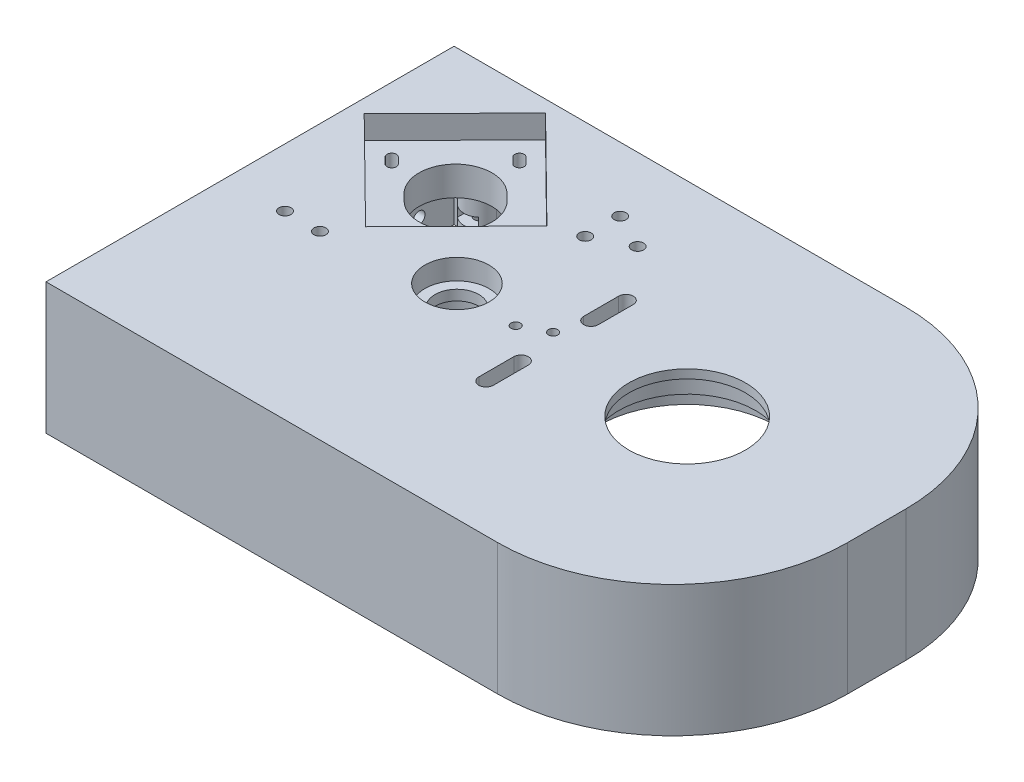
SolidWorks part; units mm, degrees
ref_plane "Front Plane" through (0, 0, 0) normal (0, 0, 1) x (1, 0, 0)
ref_plane "Top Plane" through (0, 0, 0) normal (0, 1, 0) x (1, 0, 0)
ref_plane "Right Plane" through (0, 0, 0) normal (1, 0, 0) x (0, 0, -1)
sketch "Sketch1" plane through (0, 0, 0) normal (0, 1, 0) x (1, 0, 0)
  line L1 (-107.5, -70) -> (107.5, -70)
  line L2 (-107.5, -70) -> (-107.5, 70)
  line L3 (-107.5, 70) -> (107.5, 70)
  line L4 (107.5, -70) -> (107.5, 70)
  line L5 (-107.5, -70) -> (107.5, 70) construction
  line L6 (-107.5, 70) -> (107.5, -70) construction
  point P0 (0, 0)
  dimension "D1" = 215
  dimension "D2" = 140
extrude "Boss-Extrude1" add sketch "Sketch1" along normal blind 10
fillet "Fillet1" radius 60 2 edges at (107.5, 5, -70) (107.5, 5, 70)
sketch "Sketch2" plane through (0, 10, 0) normal (0, 1, 0) x (1, 0, 0)
  line L0 (107.5, -10) -> (107.5, 10) construction
  line L1 (30.0949, 32.7279) -> (-38.981, 6.5456) construction
  line L2 (-38.981, -6.5456) -> (30.0949, -32.7279) construction
  circle A0 centre (42.5, 0) radius 20
  arc A1 (-38.981, 6.5456) -> (-38.981, -6.5456) centre (-36.5, 0) ccw construction
  circle A2 centre (-36.5, 0) radius 7.5
  arc A3 (30.0949, -32.7279) -> (30.0949, 32.7279) centre (42.5, 0) ccw construction
  dimension "D1" = 40
  dimension "D3" = 14
  dimension "D5" = 70
  dimension "D6" = 15
  dimension "D2" = 65
  dimension "D4" = 79
extrude "Cut-Extrude1" cut sketch "Sketch2" against normal through all
sketch "Sketch3" plane through (0, 10, 0) normal (0, 1, 0) x (1, 0, 0)
  line L0 (-36.5, 0) -> (-107.5, 70) construction
  line L1 (-67.0785, 38.2761) -> (-27.7732, 23.9602) construction
  line L2 (-75.2059, 30.0325) -> (-60.334, -9.0658) construction
  line L3 (-62.6172, 43.3029) -> (-60.4808, 41.1967)
  line L4 (-80.169, 25.5003) -> (-78.0327, 23.3941)
  arc A0 (-78.0327, 23.3941) -> (-60.4808, 41.1967) centre (-69.2568, 32.2954) ccw
  arc A1 (-67.0785, 38.2761) -> (-75.2059, 30.0325) centre (-69.2568, 32.2954) ccw construction
  arc A2 (-60.334, -9.0658) -> (-27.7732, 23.9602) centre (-36.5, 0) ccw construction
  arc A3 (-62.6172, 43.3029) -> (-80.169, 25.5003) centre (-71.3931, 34.4016) ccw
  dimension "D1" = 25
  dimension "D2" = 51
  dimension "D3" = 12.73
  dimension "D6" = 25
  dimension "D4" = 46
  dimension "D5" = 3
extrude "Cut-Extrude2" cut sketch "Sketch3" against normal through all
sketch "Sketch4" plane through (0, 10, 0) normal (0, 1, 0) x (1, 0, 0)
  line L0 (-47.3365, 32.2954) -> (-49.4578, 34.4167) construction
  line L1 (-91.1771, 32.2954) -> (-69.2568, 10.3751) construction
  line L2 (-91.1771, 32.2954) -> (-69.2568, 54.2157) construction
  line L3 (-69.2568, 54.2157) -> (-47.3365, 32.2954) construction
  line L4 (-69.2568, 10.3751) -> (-47.3365, 32.2954) construction
  line L5 (-91.1771, 32.2954) -> (-47.3365, 32.2954) construction
  line L6 (-69.2568, 54.2157) -> (-69.2568, 10.3751) construction
  line L7 (-48.4678, 31.164) -> (-50.5892, 33.2854)
  line L8 (-46.2051, 33.4268) -> (-48.3264, 35.5481)
  line L9 (-69.2568, 54.2157) -> (-71.3781, 56.337) construction
  line L10 (-70.3881, 53.0844) -> (-72.5095, 55.2057)
  line L11 (-68.1254, 55.3471) -> (-70.2467, 57.4684)
  line L12 (-69.2568, 10.3751) -> (-71.3781, 12.4964) construction
  line L13 (-70.3881, 9.2437) -> (-72.5095, 11.3651)
  line L14 (-68.1254, 11.5065) -> (-70.2467, 13.6278)
  line L15 (-91.1771, 32.2954) -> (-93.2984, 34.4167) construction
  line L16 (-92.3085, 31.164) -> (-94.4298, 33.2854)
  line L17 (-90.0457, 33.4268) -> (-92.167, 35.5481)
  line L18 (47.5, 70) -> (-107.5, 70) construction
  arc A0 (-48.4678, 31.164) -> (-46.2051, 33.4268) centre (-47.3365, 32.2954) ccw
  arc A1 (-48.3264, 35.5481) -> (-50.5892, 33.2854) centre (-49.4578, 34.4167) ccw
  arc A2 (-70.3881, 53.0844) -> (-68.1254, 55.3471) centre (-69.2568, 54.2157) ccw
  arc A3 (-70.2467, 57.4684) -> (-72.5095, 55.2057) centre (-71.3781, 56.337) ccw
  arc A4 (-70.3881, 9.2437) -> (-68.1254, 11.5065) centre (-69.2568, 10.3751) ccw
  arc A5 (-70.2467, 13.6278) -> (-72.5095, 11.3651) centre (-71.3781, 12.4964) ccw
  arc A6 (-92.3085, 31.164) -> (-90.0457, 33.4268) centre (-91.1771, 32.2954) ccw
  arc A7 (-92.167, 35.5481) -> (-94.4298, 33.2854) centre (-93.2984, 34.4167) ccw
  point P0 (-69.2568, 32.2954)
  point P6 (-48.3971, 33.3561)
  point P12 (-70.3174, 55.2764)
  point P18 (-70.3174, 11.4358)
  point P24 (-92.2377, 33.3561)
  dimension "D3" = 1.6
  dimension "D5" = 1.6
  dimension "D7" = 1.6
  dimension "D9" = 1.6
  dimension "D1" = 31
  dimension "D2" = 31
  dimension "D4" = 3
  dimension "D6" = 3
  dimension "D8" = 3
  dimension "D10" = 3
  dimension "D11" = 45
extrude "Cut-Extrude3" cut sketch "Sketch4" against normal through all
sketch "Sketch5" plane through (0, 10, 0) normal (0, 1, 0) x (1, 0, 0)
  circle A0 centre (-36.5, 0) radius 11
  dimension "D1" = 22
extrude "Cut-Extrude4" cut sketch "Sketch5" against normal blind 7
sketch "Sketch6" plane through (0, 0, 0) normal (0, -1, 0) x (1, 0, 0)
  circle A0 centre (-36.5, 0) radius 11
  circle A1 centre (-36.5, 0) radius 14
  dimension "D1" = 22
  dimension "D2" = 3
extrude "Boss-Extrude2" add sketch "Sketch6" along normal blind 8.5
sketch "Sketch7" plane through (0, 0, 0) normal (0, -1, 0) x (1, 0, 0)
  circle A0 centre (42.5, 0) radius 23.5
  dimension "D1" = 47
extrude "Cut-Extrude5" cut sketch "Sketch7" against normal blind 7
sketch "Sketch8" plane through (0, 0, 0) normal (0, -1, 0) x (1, 0, 0)
  circle A0 centre (42.5, 0) radius 30.5
  circle A1 centre (42.5, 0) radius 38.5
  dimension "D1" = 61
  dimension "D2" = 8
extrude "Boss-Extrude3" add sketch "Sketch8" along normal blind 8
sketch "Sketch9" plane through (0, 0, 0) normal (0, -1, 0) x (1, 0, 0)
  line L0 (47.5, 62) -> (-99.5, 62)
  line L1 (-99.5, 62) -> (-99.5, -62)
  line L2 (-99.5, -62) -> (47.5, -62)
  line L3 (99.5, -10) -> (99.5, 10)
  line L4 (-107.5, -70) -> (47.5, -70)
  line L5 (107.5, -10) -> (107.5, 10)
  line L6 (47.5, 70) -> (-107.5, 70)
  line L7 (-107.5, 70) -> (-107.5, -70)
  line L8 (-107.5, -70) -> (47.5, -70)
  line L9 (107.5, -10) -> (107.5, 10)
  line L10 (47.5, 70) -> (-107.5, 70)
  line L11 (-107.5, 70) -> (-107.5, -70)
  arc A0 (47.5, -62) -> (99.5, -10) centre (47.5, -10) ccw
  arc A1 (99.5, 10) -> (47.5, 62) centre (47.5, 10) ccw
  arc A2 (47.5, -70) -> (107.5, -10) centre (47.5, -10) ccw
  arc A3 (107.5, 10) -> (47.5, 70) centre (47.5, 10) ccw
  arc A4 (47.5, -70) -> (107.5, -10) centre (47.5, -10) ccw
  arc A5 (107.5, 10) -> (47.5, 70) centre (47.5, 10) ccw
  dimension "D1" = 0
  dimension "D2" = 8
extrude "Boss-Extrude4" add sketch "Sketch9" along normal blind 35
sketch "Sketch10" plane through (0, 0, 0) normal (0, -1, 0) x (1, 0, 0)
  line L0 (-36.5, -14) -> (-36.5, -62)
  line L1 (-99.5, -62) -> (47.5, -62) construction
  line L2 (-50.5, 0) -> (-99.5, 0)
  line L3 (-99.5, 62) -> (-99.5, -62) construction
  line L4 (-99.5, 0) -> (-99.5, -62)
  line L5 (-99.5, -62) -> (-36.5, -62)
  line L6 (-80.169, -25.5003) -> (-78.0327, -23.3941) construction
  line L7 (-80.169, -25.5003) -> (-78.0327, -23.3941)
  line L8 (-60.4808, -41.1967) -> (-62.6172, -43.3029) construction
  line L9 (-94.4298, -33.2854) -> (-92.3085, -31.164) construction
  line L10 (-90.0457, -33.4268) -> (-92.167, -35.5481) construction
  line L11 (-68.1254, -55.3471) -> (-70.2467, -57.4684) construction
  line L12 (-72.5095, -55.2057) -> (-70.3881, -53.0844) construction
  line L13 (-46.2051, -33.4268) -> (-48.3264, -35.5481) construction
  line L14 (-50.5892, -33.2854) -> (-48.4678, -31.164) construction
  line L15 (-68.1254, -11.5065) -> (-70.2467, -13.6278) construction
  line L16 (-72.5095, -11.3651) -> (-70.3881, -9.2437) construction
  line L17 (-60.4808, -41.1967) -> (-62.6172, -43.3029)
  line L18 (-94.4298, -33.2854) -> (-92.3085, -31.164)
  line L19 (-90.0457, -33.4268) -> (-92.167, -35.5481)
  line L20 (-68.1254, -55.3471) -> (-70.2467, -57.4684)
  line L21 (-72.5095, -55.2057) -> (-70.3881, -53.0844)
  line L22 (-46.2051, -33.4268) -> (-48.3264, -35.5481)
  line L23 (-50.5892, -33.2854) -> (-48.4678, -31.164)
  line L24 (-68.1254, -11.5065) -> (-70.2467, -13.6278)
  line L25 (-72.5095, -11.3651) -> (-70.3881, -9.2437)
  circle A0 centre (-36.5, 0) radius 14 construction
  circle A1 centre (-36.5, 0) radius 14 construction
  arc A2 (-50.5, 0) -> (-36.5, -14) centre (-36.5, 0) ccw
  arc A3 (-60.4808, -41.1967) -> (-78.0327, -23.3941) centre (-69.2568, -32.2954) ccw construction
  arc A4 (-80.169, -25.5003) -> (-62.6172, -43.3029) centre (-71.3931, -34.4016) ccw construction
  arc A5 (-90.0457, -33.4268) -> (-92.3085, -31.164) centre (-91.1771, -32.2954) ccw construction
  arc A6 (-94.4298, -33.2854) -> (-92.167, -35.5481) centre (-93.2984, -34.4167) ccw construction
  arc A7 (-72.5095, -55.2057) -> (-70.2467, -57.4684) centre (-71.3781, -56.337) ccw construction
  arc A8 (-68.1254, -55.3471) -> (-70.3881, -53.0844) centre (-69.2568, -54.2157) ccw construction
  arc A9 (-50.5892, -33.2854) -> (-48.3264, -35.5481) centre (-49.4578, -34.4167) ccw construction
  arc A10 (-46.2051, -33.4268) -> (-48.4678, -31.164) centre (-47.3365, -32.2954) ccw construction
  arc A11 (-72.5095, -11.3651) -> (-70.2467, -13.6278) centre (-71.3781, -12.4964) ccw construction
  arc A12 (-68.1254, -11.5065) -> (-70.3881, -9.2437) centre (-69.2568, -10.3751) ccw construction
  arc A13 (-60.4808, -41.1967) -> (-78.0327, -23.3941) centre (-69.2568, -32.2954) ccw
  arc A14 (-80.169, -25.5003) -> (-62.6172, -43.3029) centre (-71.3931, -34.4016) ccw
  arc A15 (-90.0457, -33.4268) -> (-92.3085, -31.164) centre (-91.1771, -32.2954) ccw
  arc A16 (-94.4298, -33.2854) -> (-92.167, -35.5481) centre (-93.2984, -34.4167) ccw
  arc A17 (-72.5095, -55.2057) -> (-70.2467, -57.4684) centre (-71.3781, -56.337) ccw
  arc A18 (-68.1254, -55.3471) -> (-70.3881, -53.0844) centre (-69.2568, -54.2157) ccw
  arc A19 (-50.5892, -33.2854) -> (-48.3264, -35.5481) centre (-49.4578, -34.4167) ccw
  arc A20 (-46.2051, -33.4268) -> (-48.4678, -31.164) centre (-47.3365, -32.2954) ccw
  arc A21 (-72.5095, -11.3651) -> (-70.2467, -13.6278) centre (-71.3781, -12.4964) ccw
  arc A22 (-68.1254, -11.5065) -> (-70.3881, -9.2437) centre (-69.2568, -10.3751) ccw
extrude "Boss-Extrude5" add sketch "Sketch10" along normal blind 8
sketch "Sketch11" plane through (0, 10, 0) normal (0, 1, 0) x (1, 0, 0)
  line L0 (-36.5, 0) -> (-107.5, 70) construction
  line L1 (-102.8611, 34.532) -> (-71.9698, 65.8646)
  line L2 (-71.9698, 65.8646) -> (-38.1449, 32.5161)
  line L3 (-38.1449, 32.5161) -> (-69.0361, 1.1835)
  line L4 (-69.0361, 1.1835) -> (-102.8611, 34.532)
  dimension "D1" = 44
  dimension "D2" = 47.5
  dimension "D3" = 24
  dimension "D4" = 22
extrude "Cut-Extrude6" cut sketch "Sketch11" against normal blind 8
sketch "Sketch12" plane through (0, 0, 0) normal (0, -1, 0) x (1, 0, 0)
  circle A0 centre (-36.5, 0) radius 7.5 construction
  circle A1 centre (-36.5, 0) radius 11
  circle A2 centre (-36.5, 0) radius 11
  circle A3 centre (-36.5, 0) radius 7.5
  dimension "D1" = 0
extrude "Boss-Extrude6" add sketch "Sketch12" along normal blind 0.5
sketch "Sketch14" plane through (0, -35, 0) normal (0, -1, 0) x (1, 0, 0)
  line L0 (99.5, -10) -> (99.5, 10) construction
  line L1 (99.5, -10) -> (99.5, 10)
  line L2 (42.5, 0) -> (99.5, 0) construction
  line L3 (42.5, 0) -> (95.1611, 21.813) construction
  line L4 (42.5, 0) -> (65.461, 55.4328) construction
  line L5 (60.3335, 57.5567) -> (61.3912, 60.1102)
  line L6 (70.5885, 53.3089) -> (71.7114, 56.0197)
  line L7 (93.0372, 26.9405) -> (96.1931, 28.2477)
  line L8 (97.285, 16.6854) -> (98.973, 17.3846)
  arc A0 (47.5, -62) -> (99.5, -10) centre (47.5, -10) ccw construction
  arc A1 (99.5, 10) -> (47.5, 62) centre (47.5, 10) ccw construction
  arc A2 (47.5, -62) -> (99.5, -10) centre (47.5, -10) ccw
  arc A3 (99.5, 10) -> (47.5, 62) centre (47.5, 10) ccw
  circle A4 centre (65.461, 55.4328) radius 2.05
  circle A5 centre (95.1611, 21.813) radius 2.05
  arc A6 (60.3335, 57.5567) -> (70.5885, 53.3089) centre (65.461, 55.4328) ccw
  arc A7 (93.0372, 26.9405) -> (97.285, 16.6854) centre (95.1611, 21.813) ccw
  circle A8 centre (65.461, 55.4328) radius 5.55 construction
  circle A9 centre (95.1611, 21.813) radius 5.55 construction
  arc M12 (47.5, 62) -> (99.5, 10) centre (47.5, 10) cw
  dimension "D5" = 4.1
  dimension "D6" = 4.1
  dimension "D1" = 22.5
  dimension "D2" = 67.5
  dimension "D3" = 57
  dimension "D4" = 60
  dimension "D7" = 3.5
extrude "Boss-Extrude7" add sketch "Sketch14" against normal up to next contours L5 A6 L6 A4 M12 | L7 A7 L8 A5 M12 region at (97.7294, -35, 22.8536) region at (61.0066, -35, 58.7737)
ref_plane "Plane1" through (0, -25, 0) normal (0, -1, 0) x (-1, 0, 0)
sketch "Sketch15" plane through (0, -25, 0) normal (0, -1, 0) x (-1, 0, 0)
  line L0 (-70.5885, -53.3089) -> (-71.7114, -56.0197) construction
  line L1 (-92.6363, -16.8705) -> (-98.459, -19.2824)
  line L2 (-98.459, -19.2824) -> (-99.0016, -23.4037)
  line L3 (-99.0016, -23.4037) -> (-95.7037, -25.9343)
  line L4 (-95.7037, -25.9343) -> (-89.881, -23.5225)
  line L7 (-67.1705, -50.1526) -> (-69.5824, -55.9754)
  line L8 (-69.5824, -55.9754) -> (-67.0518, -59.2733)
  line L9 (-67.0518, -59.2733) -> (-62.9304, -58.7307)
  line L10 (-62.9304, -58.7307) -> (-60.5186, -52.9079)
  line L13 (-98.973, -17.3846) -> (-97.285, -16.6854) construction
  line L14 (-91.3206, -20.2222) -> (-92.9696, -18.9569) [skipped]
  line L15 (-91.8632, -24.3435) -> (-91.5919, -22.2828) [skipped]
  line L16 (-61.3396, -54.8902) -> (-62.6049, -53.2412) [skipped]
  line L17 (-65.9309, -51.8636) -> (-67.9916, -52.1349) [skipped]
  circle A0 centre (-95.1611, -21.813) radius 3.6 construction
  circle A1 centre (-65.461, -55.4328) radius 3.6 construction
  arc A2 (-60.3335, -57.5567) -> (-70.5885, -53.3089) centre (-65.461, -55.4328) ccw construction
  arc A3 (-60.5186, -52.9079) -> (-67.1705, -50.1526) centre (-65.461, -55.4328) ccw
  arc A4 (-93.0372, -26.9405) -> (-97.285, -16.6854) centre (-95.1611, -21.813) ccw construction
  arc A5 (-89.881, -23.5225) -> (-92.6363, -16.8705) centre (-95.1611, -21.813) ccw
  dimension "D1" = 7.2
  dimension "D2" = 7.2
extrude "Cut-Extrude7" cut sketch "Sketch15" against normal blind 3.6
mirror "Mirror1" about plane through (0, 0, 0) normal (0, 0, 1) of "Cut-Extrude7", "Boss-Extrude7"
sketch "Sketch16" plane through (0, -35, 0) normal (0, -1, 0) x (1, 0, 0)
  line L0 (42.5, 0) -> (0, 0) construction
  line L1 (22.5, 0) -> (22.5, 59) construction
  line L2 (16.95, 59) -> (16.95, 62)
  line L3 (47.5, 62) -> (-99.5, 62) construction
  line L4 (16.95, 62) -> (28.05, 62)
  line L5 (47.5, 62) -> (-99.5, 62) construction
  line L6 (28.05, 62) -> (28.05, 59)
  circle A0 centre (22.5, 59) radius 2.05
  arc A1 (16.95, 59) -> (28.05, 59) centre (22.5, 59) ccw
  circle A2 centre (22.5, 59) radius 5.55 construction
  dimension "D3" = 4.1
  dimension "D1" = 59
  dimension "D2" = 20
  dimension "D4" = 3.5
extrude "Boss-Extrude8" add sketch "Sketch16" against normal up to next
sketch "Sketch17" plane through (0, -25, 0) normal (0, -1, 0) x (-1, 0, 0)
  line L0 (-16.95, -59) -> (-16.95, -62) construction
  line L3 (-26.1, -54.776) -> (-26.1, -61.0785)
  line L4 (-26.1, -61.0785) -> (-22.5, -63.1569)
  line L5 (-22.5, -63.1569) -> (-18.9, -61.0785)
  line L6 (-18.9, -61.0785) -> (-18.9, -54.776)
  line L7 (-20.7, -55.8823) -> (-22.5, -54.8431) [skipped]
  line L8 (-24.3, -55.8823) -> (-26.1, -56.9215) [skipped]
  arc A1 (-16.95, -59) -> (-28.05, -59) centre (-22.5, -59) ccw construction
  arc A2 (-16.95, -59) -> (-28.05, -59) centre (-22.5, -59) ccw
  dimension "D1" = 7.2
extrude "Cut-Extrude8" cut sketch "Sketch17" against normal blind 3.6 contours L6 A2 L3 L4 L5 region at (22.5, -25, 58.0058)
pattern_linear "LPattern1" count 3 spacing 55 along (-1, 0, 0) of "Cut-Extrude8", "Boss-Extrude8"
mirror "Mirror2" about plane through (0, 0, 0) normal (0, 0, 1) of "LPattern1", "Boss-Extrude8", "Cut-Extrude8"
sketch "Sketch18" plane through (0, -35, 0) normal (0, -1, 0) x (1, 0, 0)
  line L0 (-107.5, 70) -> (-107.5, -70) construction
  line L1 (-96.5, 28.55) -> (-99.5, 28.55)
  line L2 (-99.5, 62) -> (-99.5, -62) construction
  line L3 (-99.5, 28.55) -> (-99.5, 17.45)
  line L4 (-99.5, 17.45) -> (-96.5, 17.45)
  circle A0 centre (-96.5, 23) radius 2.05
  arc A1 (-96.5, 17.45) -> (-96.5, 28.55) centre (-96.5, 23) ccw
  circle A2 centre (-96.5, 23) radius 5.55 construction
  dimension "D1" = 4.1
  dimension "D3" = 23
  dimension "D4" = 11
  dimension "D2" = 3.5
extrude "Boss-Extrude9" add sketch "Sketch18" against normal up to next
sketch "Sketch19" plane through (0, -25, 0) normal (0, -1, 0) x (-1, 0, 0)
  line L0 (99.5, -17.45) -> (96.5, -17.45) construction
  line L1 (98.5785, -19.4) -> (92.276, -19.4)
  line L4 (92.276, -26.6) -> (98.5785, -26.6)
  line L5 (98.5785, -26.6) -> (100.6569, -23)
  line L6 (100.6569, -23) -> (98.5785, -19.4)
  line L7 (92.3431, -23) -> (93.3823, -24.8) [skipped]
  line L8 (94.4215, -19.4) -> (93.3823, -21.2) [skipped]
  circle A0 centre (96.5, -23) radius 3.6 construction
  arc A1 (96.5, -17.45) -> (96.5, -28.55) centre (96.5, -23) ccw construction
  arc A2 (92.276, -19.4) -> (92.276, -26.6) centre (96.5, -23) ccw
  dimension "D1" = 7.2
extrude "Cut-Extrude9" cut sketch "Sketch19" against normal blind 3.6
mirror "Mirror3" about plane through (0, 0, 0) normal (0, 0, 1) of "Boss-Extrude9", "Cut-Extrude9"
sketch "Sketch20" plane through (0, 0, 0) normal (0, -1, 0) x (1, 0, 0)
  line L0 (-26.95, -62) -> (16.95, -62) construction
  line L1 (45.3284, 2.8284) -> (-16.6716, 64.8284) construction
  line L2 (28.05, -62) -> (47.5, -62) construction
  line L3 (99.5, -10) -> (99.5, 10) construction
  line L4 (45.3284, -2.8284) -> (-16.6716, -64.8284) construction
  line L5 (47.5, 62) -> (28.05, 62) construction
  line L7 (16.95, 62) -> (-26.95, 62) construction
  line L8 (-26.95, -62) -> (16.95, -62)
  line L10 (28.05, -62) -> (47.5, -62)
  line L12 (99.5, -10) -> (99.5, 10)
  line L13 (47.5, 62) -> (28.05, 62)
  line L14 (16.95, 62) -> (-26.95, 62)
  line L15 (42.5, 0) -> (99.5, 0) construction
  line L16 (42.5, 0) -> (86.6845, 44.1845) construction
  line L17 (42.5, 0) -> (86.6845, -44.1845) construction
  line L18 (42.5, 0) -> (-19.5, -62) construction
  line L19 (42.5, 0) -> (-19.5, 62) construction
  line L20 (42.5, 0) -> (42.5, 62) construction
  line L21 (42.5, 0) -> (42.5, -62) construction
  line L22 (45.3284, 2.8284) -> (-13.8431, 62)
  line L23 (46.5, 0) -> (46.5, 62)
  line L24 (45.3284, -2.8284) -> (89.5129, 41.356)
  line L25 (42.5, -4) -> (99.5, -4)
  line L26 (39.6716, -2.8284) -> (83.9397, -47.0965)
  line L27 (38.5, 0) -> (38.5, -62)
  line L28 (39.6716, 2.8284) -> (-25.1569, -62)
  line L29 (39.6716, -2.8284) -> (-25.1569, 62)
  line L30 (38.5, 0) -> (38.5, 62)
  line L31 (39.6716, 2.8284) -> (83.9397, 47.0965)
  line L32 (42.5, 4) -> (99.5, 4)
  line L33 (45.3284, 2.8284) -> (89.5129, -41.356)
  line L34 (46.5, 0) -> (46.5, -62)
  line L35 (45.3284, -2.8284) -> (-13.8431, -62)
  line L36 (39.6716, -2.8284) -> (-22.3284, 59.1716) construction
  line L37 (39.6716, 2.8284) -> (-22.3284, -59.1716) construction
  line L38 (39.6716, -2.8284) -> (83.856, -47.0129) construction
  line L39 (39.6716, 2.8284) -> (83.856, 47.0129) construction
  circle A0 centre (42.5, 0) radius 38.5
  circle A1 centre (42.5, 0) radius 38.5 construction
  arc A2 (71.7114, -56.0197) -> (96.1931, -28.2477) centre (47.5, -10) ccw construction
  arc A3 (96.1931, 28.2477) -> (71.7114, 56.0197) centre (47.5, 10) ccw construction
  arc A4 (71.7114, -56.0197) -> (96.1931, -28.2477) centre (47.5, -10) ccw
  arc A5 (96.1931, 28.2477) -> (71.7114, 56.0197) centre (47.5, 10) ccw
  arc M32 (71.7114, -56.0197) -> (96.1931, -28.2477) centre (47.5, -10) ccw
  arc M42 (96.1931, 28.2477) -> (71.7114, 56.0197) centre (47.5, 10) ccw
  circle M63 centre (42.5, 0) radius 38.5
  dimension "D1" = 45
  dimension "D2" = 45
  dimension "D3" = 45
  dimension "D4" = 45
  dimension "D5" = 4
  dimension "D6" = 4
extrude "Boss-Extrude10" add sketch "Sketch20" along normal up to surface (8 mm away) contours L29 L22 L14 M63 | L30 L23 L13 M63 | L31 L24 M63 M42 | L32 L25 L12 M63 | L33 L26 M63 M32 | L34 L27 L10 M63 | L35 L28 L8 M63 region at (-2.2021, 0, -44.549) region at (-2.2021, 0, 44.549) region at (42.5, 0, -50.2152) region at (42.5, 0, 50.2152) region at (78.1509, 0, -35.6723) region at (78.1509, 0, 35.6723) region at (90.2152, 0, 0) up to face at (42.5, -8, -38.5)
sketch "Sketch21" plane through (0, 0, 0) normal (0, -1, 0) x (1, 0, 0)
  line L0 (-2.5, 12) -> (-2.5, 24) construction
  line L1 (-5, 12) -> (-5, 24)
  line L2 (0, 12) -> (0, 24)
  line L3 (-2.5, -12) -> (-2.5, -24) construction
  line L4 (0, -12) -> (0, -24)
  line L5 (-5, -12) -> (-5, -24)
  arc A0 (-5, 12) -> (0, 12) centre (-2.5, 12) ccw
  arc A1 (0, 24) -> (-5, 24) centre (-2.5, 24) ccw
  arc A2 (0, -12) -> (-5, -12) centre (-2.5, -12) ccw
  arc A3 (-5, -24) -> (0, -24) centre (-2.5, -24) ccw
  circle A4 centre (-36.5, 0) radius 7.5 construction
  point P2 (-2.5, 18)
  point P7 (-2.5, -18)
  dimension "D1" = 2.5
  dimension "D2" = 2.5
  dimension "D5" = 34
  dimension "D3" = 12
  dimension "D4" = 12
  dimension "D6" = 12
  dimension "D7" = 12
extrude "Cut-Extrude10" cut sketch "Sketch21" against normal through all
sketch "Sketch22" plane through (0, 0, 0) normal (0, -1, 0) x (1, 0, 0)
  line L0 (-13.888, 2.46) -> (-5.5, -2) construction
  line L1 (-81.95, -62) -> (-38.05, -62) construction
  circle A0 centre (-5.5, -2) radius 1.6
  circle A1 centre (-13.888, 2.46) radius 1.6
  circle A2 centre (-36.5, 0) radius 7.5 construction
  dimension "D4" = 3.2
  dimension "D5" = 3.2
  dimension "D1" = 31
  dimension "D2" = 2
  dimension "D3" = 9.5
  dimension "D6" = 28
extrude "Cut-Extrude11" cut sketch "Sketch22" against normal through all
sketch "Sketch23" plane through (0, 0, 0) normal (0, -1, 0) x (1, 0, 0)
  line L0 (-99.5, 17.45) -> (-99.5, -17.45) construction
  line L1 (-50.5, 0) -> (-99.5, 0) construction
  line L2 (-36.5, -55.1526) -> (-36.5, -14) construction
  line L3 (-26.95, -62) -> (16.95, -62) construction
  circle A0 centre (-87.5, 8) radius 2.05
  circle A1 centre (-75.5, 8) radius 2.05
  circle A2 centre (-28.5, -36) radius 2.05
  circle A3 centre (-28.5, -48) radius 2.05
  circle A4 centre (-16.5, -42) radius 2.05
  dimension "D4" = 4.1
  dimension "D5" = 4.1
  dimension "D6" = 4.1
  dimension "D7" = 4.1
  dimension "D8" = 4.1
  dimension "D1" = 12
  dimension "D2" = 12
  dimension "D3" = 8
  dimension "D9" = 8
  dimension "D10" = 12
  dimension "D11" = 20
  dimension "D12" = 20
  dimension "D13" = 14
extrude "Cut-Extrude12" cut sketch "Sketch23" against normal through all
sketch "Sketch24" plane through (-107.5, 0, 0) normal (-1, 0, 0) x (0, 0, 1)
  line L0 (70, -35) -> (-70, -35) construction
  line L1 (70, 10) -> (70, -35) construction
  line L2 (-70, 10) -> (-70, -35) construction
  circle A0 centre (0, -27) radius 2.05
  circle A1 centre (0, -13) radius 2.05
  circle A2 centre (-50, -13) radius 2.05
  circle A3 centre (-50, -27) radius 2.05
  circle A4 centre (50, -13) radius 2.05
  circle A5 centre (50, -27) radius 2.05
  dimension "D1" = 4.1
  dimension "D2" = 4.1
  dimension "D5" = 4.1
  dimension "D6" = 4.1
  dimension "D8" = 4.1
  dimension "D9" = 4.1
  dimension "D3" = 8
  dimension "D4" = 14
  dimension "D7" = 20
  dimension "D10" = 20
extrude "Cut-Extrude13" cut sketch "Sketch24" against normal up to next
